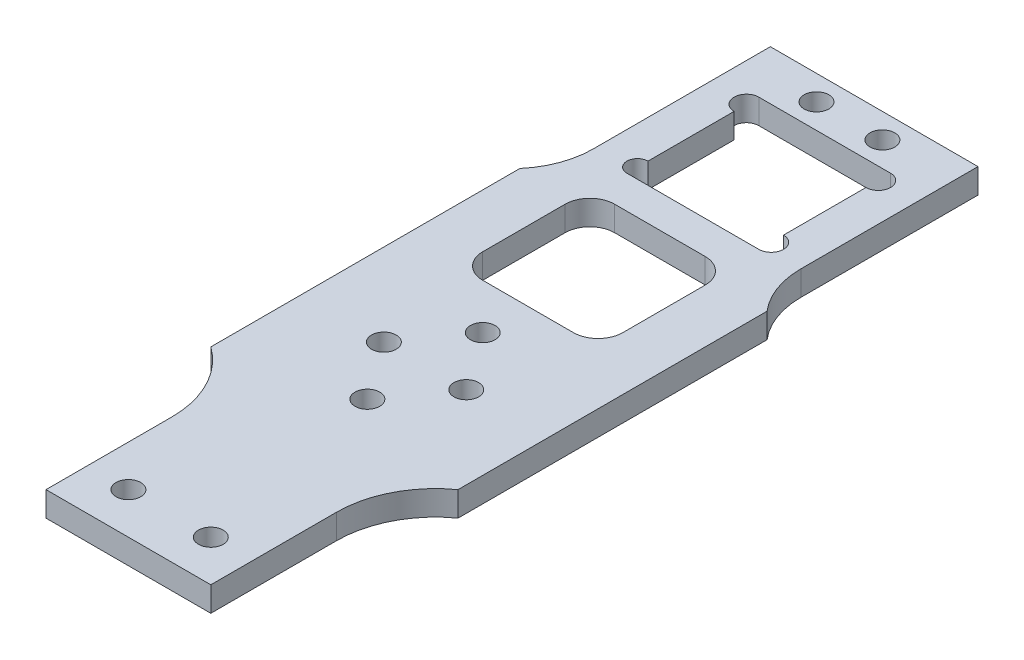
SolidWorks part; units mm, degrees
material "Thornel Mat VMA"
ref_plane "前视基准面" through (0, 0, 0) normal (0, 0, 1) x (1, 0, 0)
ref_plane "上视基准面" through (0, 0, 0) normal (0, 1, 0) x (1, 0, 0)
ref_plane "右视基准面" through (0, 0, 0) normal (1, 0, 0) x (0, 0, -1)
sketch "草图1" plane through (0, 0, 0) normal (0, 1, 0) x (1, 0, 0)
  line L1 (-12.6, -14) -> (12.6, -14)
  line L2 (-12.6, -14) -> (-12.6, 14)
  line L3 (-12.6, 14) -> (12.6, 14)
  line L4 (12.6, -14) -> (12.6, 14)
  line L5 (-12.6, -14) -> (12.6, 14) construction
  line L6 (-12.6, 14) -> (12.6, -14) construction
  point P0 (0, 0)
  dimension "D1" = 28
  dimension "D2" = 25.2
extrude "凸台-拉伸1" add sketch "草图1" along normal blind 3
sketch "草图4" plane through (0, 3, 0) normal (0, 1, 0) x (1, 0, 0)
  line L0 (0, 14) -> (0, 11) construction
  line L1 (12.6, 14) -> (-12.6, 14) construction
  line L2 (0, 11) -> (4, 11) construction
  line L3 (4, 11) -> (-4, 11) construction
  line L4 (0, 14) -> (0, 8) construction
  line L5 (0, 8) -> (8, 8) construction
  line L7 (8, 8) -> (-8, 8)
  line L8 (8, 8) -> (8, -8)
  line L9 (8, -8) -> (-8, -8)
  line L10 (-8, 8) -> (-8, -8)
  circle A0 centre (4, 11) radius 1.5
  circle A1 centre (-4, 11) radius 1.5
  dimension "D4" = 3
  dimension "D5" = 3
  dimension "D1" = 3
  dimension "D2" = 4
  dimension "D3" = 8
  dimension "D6" = 6
  dimension "D7" = 8
  dimension "D8" = 16
extrude "切除-拉伸3" cut sketch "草图4" against normal through all
sketch "草图5" plane through (0, 3, 0) normal (0, 1, 0) x (1, 0, 0)
  line L0 (8, -8) -> (8, 8) construction
  line L1 (-8, 8) -> (-8, -8) construction
  line L2 (8, 8) -> (-8, 8) construction
  line L4 (-8, -8) -> (8, -8) construction
  circle A4 centre (8, 6.5) radius 1.5
  circle A5 centre (-8, 6.5) radius 1.5
  circle A6 centre (8, -6.5) radius 1.5
  circle A7 centre (-8, -6.725) radius 1.275
  dimension "D1" = 3
  dimension "D2" = 2.55
  dimension "D3" = 3
  dimension "D4" = 3
sketch "草图6" plane through (0, 3, 0) normal (0, 1, 0) x (1, 0, 0)
  line L0 (0, -14) -> (-15, -14) construction
  line L1 (-12.6, -14) -> (12.6, -14) construction
  line L3 (-15, -14) -> (15, -14)
  line L4 (-15, -14) -> (-15, -51.5)
  line L5 (-15, -51.5) -> (15, -51.5)
  line L6 (15, -14) -> (15, -51.5)
  dimension "D1" = 15
  dimension "D2" = 37.5
  dimension "D3" = 30
extrude "凸台-拉伸2" add sketch "草图6" against normal blind 3
sketch "草图7" plane through (0, 3, 0) normal (0, 1, 0) x (1, 0, 0)
  line L0 (0, -51.5) -> (0, -47.5) construction
  line L1 (-15, -51.5) -> (15, -51.5) construction
  line L2 (0, -47.5) -> (0, -33.5) construction
  line L3 (0, -40.5) -> (-5, -40.5) construction
  line L4 (-5, -40.5) -> (5, -40.5) construction
  circle A0 centre (0, -33.5) radius 1.5
  circle A1 centre (-5, -40.5) radius 1.5
  circle A2 centre (5, -40.5) radius 1.5
  circle A3 centre (0, -47.5) radius 1.5
  dimension "D5" = 3
  dimension "D6" = 3
  dimension "D7" = 3
  dimension "D8" = 3
  dimension "D1" = 4
  dimension "D2" = 14
  dimension "D3" = 5
  dimension "D4" = 10
extrude "切除-拉伸5" cut sketch "草图7" against normal through all
fillet "圆角1" radius 10 2 edges at (12.6, 1.5, 14) (-12.6, 1.5, 14)
sketch "草图8" plane through (0, 3, 0) normal (0, 1, 0) x (1, 0, 0)
  line L0 (0, -8) -> (0, -32) construction
  line L1 (-8, -8) -> (8, -8) construction
  line L7 (-8.5, -28) -> (8.5, -28)
  line L8 (-8.5, -28) -> (-8.5, -12)
  line L9 (-8.5, -12) -> (8.5, -12)
  line L10 (8.5, -28) -> (8.5, -12)
  line L11 (-8.5, -28) -> (8.5, -12) construction
  line L12 (-8.5, -12) -> (8.5, -28) construction
  circle A0 centre (0, -33.5) radius 1.5 construction
  point P7 (0, -20)
  dimension "D1" = 16
  dimension "D2" = 17
extrude "切除-拉伸6" cut sketch "草图8" against normal through all
fillet "圆角2" radius 3 4 edges at (8.5, 1.5, 28) (-8.5, 1.5, 28) (8.5, 1.5, 12) (-8.5, 1.5, 12)
extrude "切除-拉伸7" cut sketch "草图5" against normal blind 10
sketch "草图9" plane through (0, 0, 51.5) normal (0, 0, 1) x (1, 0, 0)
  line L0 (0, 3) -> (-10, 3) construction
  line L1 (-15, 3) -> (15, 3) construction
  line L3 (-10, 3) -> (10, 3)
  line L4 (-10, 3) -> (-10, 0)
  line L5 (-10, 0) -> (10, 0)
  line L6 (10, 3) -> (10, 0)
  line L7 (-15, 0) -> (15, 0) construction
  dimension "D1" = 10
  dimension "D2" = 3
  dimension "D3" = 20
extrude "凸台-拉伸3" add sketch "草图9" along normal blind 25
fillet "圆角3" radius 12 2 edges at (10, 1.5, 51.5) (-10, 1.5, 51.5)
sketch "草图12" plane through (0, 3, 0) normal (0, 1, 0) x (1, 0, 0)
  line L0 (0, -76.5) -> (0, -71.5) construction
  line L1 (10, -76.5) -> (-10, -76.5) construction
  line L2 (0, -71.5) -> (5, -71.5) construction
  line L3 (5, -71.5) -> (-5, -71.5) construction
  circle A0 centre (5, -71.5) radius 1.5
  circle A1 centre (-5, -71.5) radius 1.5
  dimension "D4" = 3
  dimension "D5" = 3
  dimension "D1" = 5
  dimension "D2" = 5
  dimension "D3" = 10
extrude "切除-拉伸9" cut sketch "草图12" against normal through all
